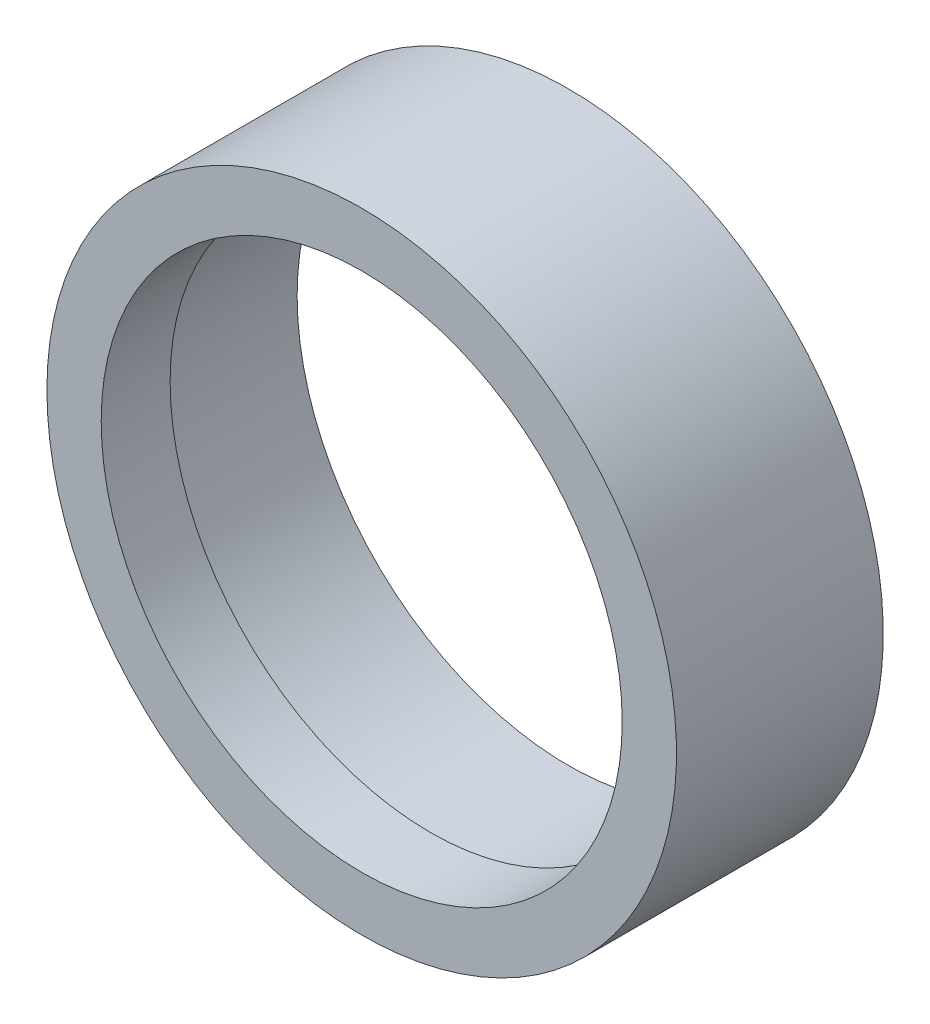
SolidWorks part; units mm, degrees
ref_plane "Front Plane" through (0, 0, 0) normal (0, 0, 1) x (1, 0, 0)
ref_plane "Top Plane" through (0, 0, 0) normal (0, 1, 0) x (1, 0, 0)
ref_plane "Right Plane" through (0, 0, 0) normal (1, 0, 0) x (0, 0, -1)
ref_axis "Axis X" through (-88.99, 0, 0) along (1, 0, 0)
ref_axis "Axis Y" through (0, 55, 0) along (0, -1, 0)
ref_axis "Axis Z" through (0, 0, -88.99) along (0, 0, 1)
sketch "Sketch1" plane through (0, 0, 0) normal (0, 0, 1) x (1, 0, 0)
  circle A0 centre (0, 0) radius 25
  circle A1 centre (0, 0) radius 29
  dimension "D1" = 50
  dimension "D2" = 58
extrude "Boss-Extrude1" add sketch "Sketch1" along normal blind 19.05
sketch "Sketch2" plane through (0, 0, 19.05) normal (0, 0, 1) x (1, 0, 0)
  circle A0 centre (0, 0) radius 24
  circle A1 centre (0, 0) radius 25
  circle A2 centre (0, 0) radius 25 construction
  dimension "D1" = 1
extrude "Boss-Extrude2" add sketch "Sketch2" against normal blind 6.35
